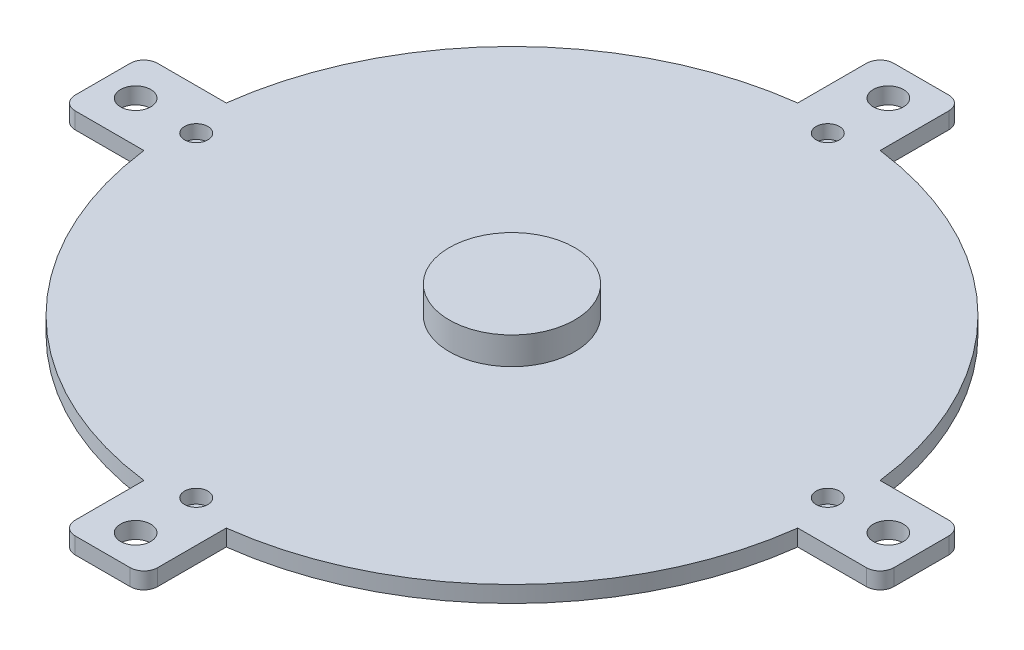
SolidWorks part; units mm, degrees
ref_plane "Front Plane" through (0, 0, 0) normal (0, 0, 1) x (1, 0, 0)
ref_plane "Top Plane" through (0, 0, 0) normal (0, 1, 0) x (1, 0, 0)
ref_plane "Right Plane" through (0, 0, 0) normal (1, 0, 0) x (0, 0, -1)
sketch "Sketch5" plane through (0, 0, 0) normal (1, 0, 0) x (0, 0, -1)
  line L0 (22.85, 6) -> (120, 6)
  line L1 (0, 0) -> (120, 0)
  line L2 (0, 0) -> (0, 16)
  line L4 (120, 0) -> (120, 6)
  line L5 (0, 16) -> (22.85, 16)
  line L8 (22.85, 16) -> (22.85, 6)
  line L9 (0, 0) -> (0, 65.0916) construction
  dimension "D1" = 45.7
  dimension "D2" = 240
  dimension "D3" = 10
  dimension "D4" = 6
revolve "Revolve1" add sketch "Sketch5" angle 360 about L9
sketch "Sketch6" plane through (0, 6, 0) normal (0, 1, 0) x (1, 0, 0)
  line L1 (-15, 119.0588) -> (15, 119.0588)
  line L2 (-15, 119.0588) -> (-15, 149.0588)
  line L3 (-15, 149.0588) -> (15, 149.0588)
  line L4 (15, 119.0588) -> (15, 149.0588)
  circle A0 centre (0, 0) radius 120 construction
  dimension "D1" = 30
  dimension "D2" = 30
extrude "Boss-Extrude3" add sketch "Sketch6" against normal through all
fillet "Fillet1" radius 5 2 edges at (-15, 3, -149.0588) (15, 3, -149.0588)
hole_wizard "M10 Clearance Hole1" positions "3DSketch1" profile "Sketch7" hole size "M10" standard "ANSI Metric" end condition through all
sketch3d "3DSketch1"
  line L0 (0, 6, -149.0588) -> (0, 6, -137.0588) construction
  line L1 (10, 6, -149.0588) -> (-10, 6, -149.0588) construction
  point P0 (0, 6, -137.0588)
  dimension "D1" = 12
sketch "Sketch7" plane through (0, 6, -137.0588) normal (1, 0, 0) x (0, 0, 1)
  line L0 (0, 0) -> (0, 6)
  line L1 (0, 6) -> (5.5, 6)
  line L2 (5.5, 6) -> (5.5, 0)
  line L5 (5.5, 0) -> (0, 0)
  line L11 (0, -6.35) -> (0, 107.95) construction
  dimension "Thru Hole Dia." = 11
  dimension "Thru Hole Depth" = 6
pattern_circular "CirPattern1" count 4 over 360 about axis through (0, 0, 0) along (0, -1, 0) of "Fillet1", "Boss-Extrude3", "M10 Clearance Hole1" reverse direction yes
sketch "Sketch8" plane through (0, 6, 0) normal (0, 1, 0) x (1, 0, 0)
  line L0 (0, 115) -> (0, 0) construction
  circle A0 centre (0, 115) radius 4.25
  dimension "D2" = 8.5
  dimension "D1" = 115
extrude "Cut-Extrude1" cut sketch "Sketch8" against normal blind 5
pattern_circular "CirPattern2" count 4 over 360 about axis through (0, 0, 0) along (0, -1, 0) of "Cut-Extrude1" reverse direction yes
